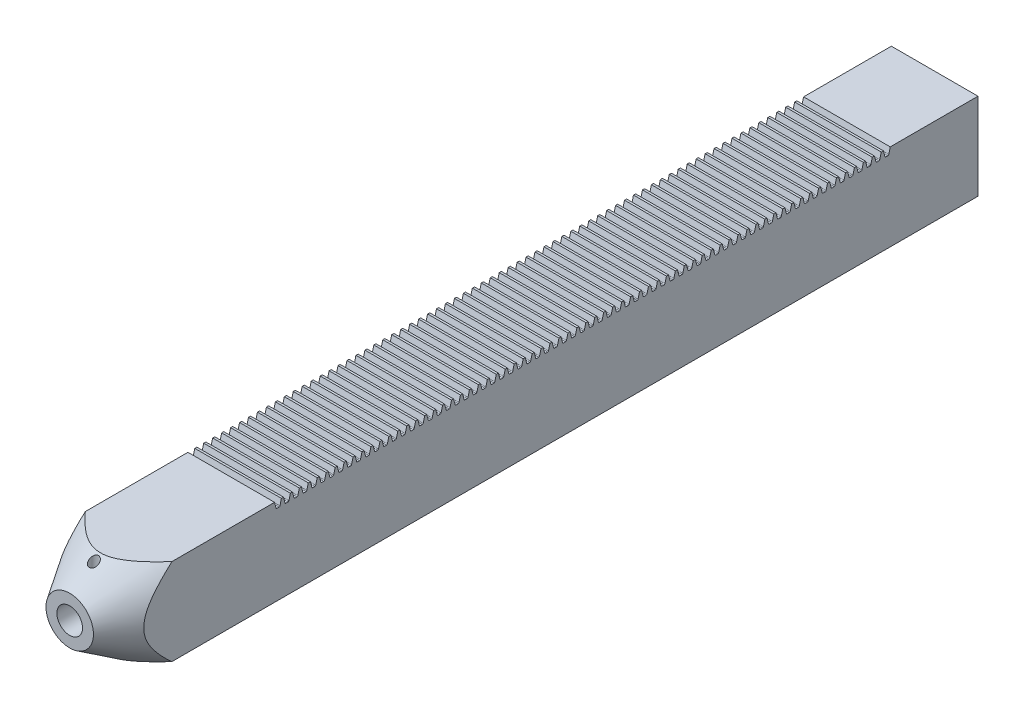
SolidWorks part; units mm, degrees
ref_plane "Front Plane" through (0, 0, 0) normal (0, 0, 1) x (1, 0, 0)
ref_plane "Top Plane" through (0, 0, 0) normal (0, 1, 0) x (1, 0, 0)
ref_plane "Right Plane" through (0, 0, 0) normal (1, 0, 0) x (0, 0, -1)
sketch "Sketch2" plane through (0, 0, 0) normal (0, 0, 1) x (1, 0, 0)
  line L1 (24.13, -24.13) -> (-24.13, -24.13)
  line L2 (24.13, -24.13) -> (24.13, 24.13)
  line L3 (24.13, 24.13) -> (-24.13, 24.13)
  line L4 (-24.13, -24.13) -> (-24.13, 24.13)
  line L5 (24.13, -24.13) -> (-24.13, 24.13) construction
  line L6 (24.13, 24.13) -> (-24.13, -24.13) construction
  point P0 (0, 0)
  dimension "D1" = 48.26
  dimension "D2" = 48.26
extrude "Boss-Extrude1" add sketch "Sketch2" along normal blind 482.6
chamfer "Chamfer1" distance 0.762 angle 45 8 edges at (0, -24.13, 0) (24.13, 0, 0) (0, 24.13, 0) (-24.13, 0, 0) (0, -24.13, 482.6) (-24.13, 0, 482.6) (24.13, 0, 482.6) (0, 24.13, 482.6)
sketch "Sketch4" plane through (24.13, 0, 0) normal (1, 0, 0) x (0, 0, -1)
  line L0 (-53.467, 24.13) -> (-52.6353, 20.9142)
  line L1 (-481.838, 24.13) -> (-0.762, 24.13) construction
  line L2 (-52.1435, 20.5334) -> (-50.9805, 20.5334)
  line L3 (-50.4887, 20.9142) -> (-49.657, 24.13)
  line L4 (-51.562, 20.5334) -> (-51.562, 17.8587) construction
  line L5 (-53.0512, 22.5221) -> (-50.0728, 22.5221) construction
  line L6 (-0.762, -24.13) -> (-0.762, 24.13) construction
  arc A0 (-50.9805, 20.5334) -> (-50.4887, 20.9142) centre (-50.9805, 21.0414) ccw
  arc A1 (-52.6353, 20.9142) -> (-52.1435, 20.5334) centre (-52.1435, 21.0414) ccw
  dimension "D3" = 0.508
  dimension "D1" = 3.5966
  dimension "D2" = 14.5
  dimension "D4" = 3.81
  dimension "D5" = 50.8
extrude "Cut-Extrude1" cut sketch "Sketch4" against normal through all and the other way through all
pattern_linear "LPattern1" count 69 spacing 4.9873 along (0, 0, 1) of "Cut-Extrude1"
hole_wizard "9/16 (0.5625) Diameter Hole1" positions "Sketch6" profile "Sketch7" hole size "9/16" standard "ANSI Inch"
sketch "Sketch6" plane through (0, 0, 482.6) normal (0, 0, 1) x (1, 0, 0)
  point P0 (0, 0)
sketch "Sketch7" plane through (0, 0, 482.6) normal (1, 0, 0) x (0, -1, 0)
  line L0 (0, 0) -> (0, 29.6924)
  line L1 (0, 29.6924) -> (7.1437, 25.4)
  line L2 (7.1437, 25.4) -> (7.1437, 0)
  line L5 (7.1437, 0) -> (0, 0)
  line L10 (0, 29.6924) -> (-7.1438, 25.4) construction
  line L11 (0, -6.35) -> (0, 107.95) construction
  dimension "Hole Dia." = 14.2875
  dimension "Hole Depth" = 25.4
  dimension "Drill Angle" = 118
hole_wizard "1/4-20 Tapped Hole1" positions "Sketch8" profile "Sketch9" tap size "1/4-20" standard "ANSI Inch" end condition up to next
sketch "Sketch8" plane through (0, 24.13, 0) normal (0, 1, 0) x (1, 0, 0)
  line L0 (-24.13, -481.838) -> (24.13, -481.838) construction
  point P0 (0, -469.138)
  dimension "D1" = 12.7
sketch "Sketch9" plane through (0, 24.13, 469.138) normal (1, 0, 0) x (0, 0, 1)
  line L0 (0, 0) -> (0, 16.9862)
  line L1 (0, 16.9862) -> (2.5527, 16.9862)
  line L2 (2.5527, 16.9862) -> (2.5527, 0)
  line L5 (2.5527, 0) -> (0, 0)
  line L11 (0, -6.35) -> (0, 107.95) construction
  dimension "Thru Tap Drill Dia." = 5.1054
  dimension "Thru Tap Drill Depth" = 16.9862
cosmetic thread "Hole Thread1" parameters "D2"=6.35
sketch "Sketch10" plane through (0, 0, 0) normal (1, 0, 0) x (0, 0, -1)
  line L0 (-482.6, 13.2185) -> (-348.6722, 98.5399)
  line L1 (-348.6722, 98.5399) -> (-482.6, 98.5399)
  line L2 (-482.6, 98.5399) -> (-482.6, 13.2185)
  line L3 (-481.838, 24.13) -> (-481.838, -24.13) construction
  line L4 (-481.838, 24.13) -> (-392.6027, 24.13) construction
  line L5 (-303.8804, 0) -> (-275.2399, 0) construction
  point P2 (-481.838, 0)
  dimension "D1" = 32.5
revolve "Cut-Revolve2" cut sketch "Sketch10" angle 360 about L5
